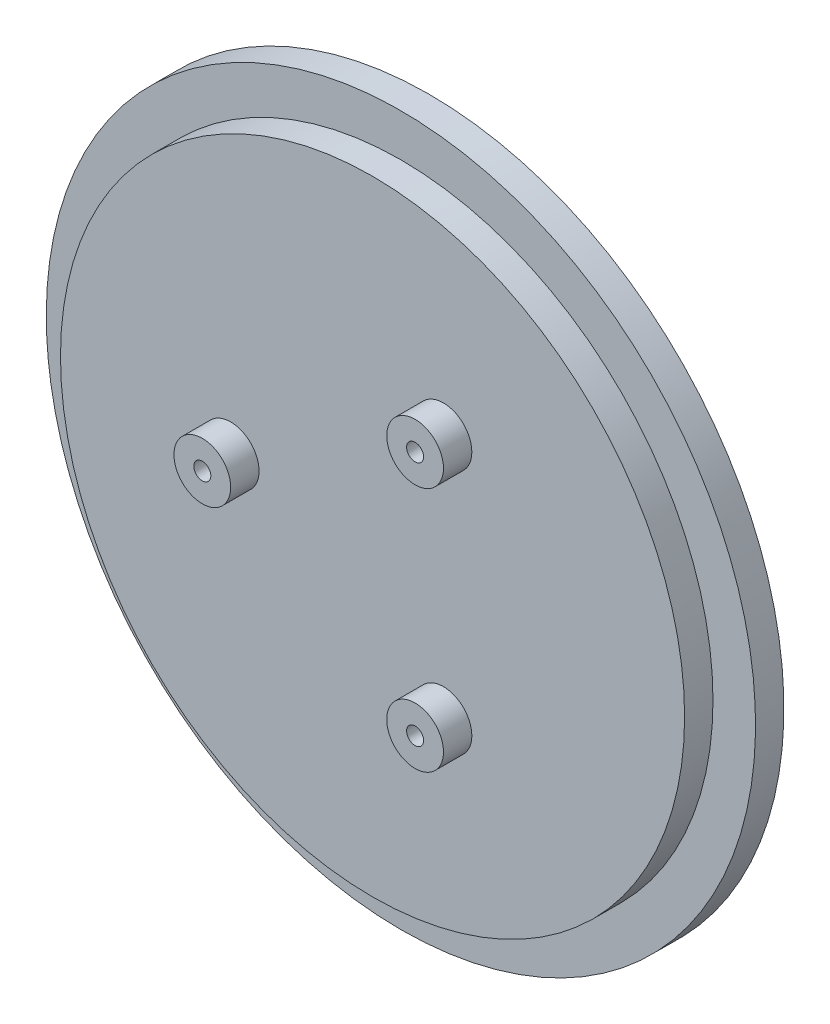
SolidWorks part; units mm, degrees
ref_plane "前视基准面" through (0, 0, 0) normal (0, 0, 1) x (1, 0, 0)
ref_plane "上视基准面" through (0, 0, 0) normal (0, 1, 0) x (1, 0, 0)
ref_plane "右视基准面" through (0, 0, 0) normal (1, 0, 0) x (0, 0, -1)
sketch "草图1" plane through (0, 0, 0) normal (0, 0, 1) x (1, 0, 0)
  circle A0 centre (0, 0) radius 22
extrude "凸台-拉伸1" add sketch "草图1" along normal blind 2
sketch "草图2" plane through (0, 0, 2) normal (0, 0, 1) x (1, 0, 0)
  circle A1 centre (-10, 0) radius 0.6
  circle A2 centre (5, -8.6603) radius 0.6
  circle A3 centre (5, 8.6603) radius 0.6
  circle A4 centre (-10, 0) radius 2
  circle A5 centre (5, 8.6603) radius 2
  circle A6 centre (5, -8.6603) radius 2
extrude "凸台-拉伸2" add sketch "草图2" along normal blind 4
sketch "草图3" plane through (0, 0, 0) normal (0, 0, -1) x (-1, 0, 0)
  circle A0 centre (0, 0) radius 25
extrude "凸台-拉伸3" add sketch "草图3" along normal blind 2
sketch "草图4" plane through (0, 0, -2) normal (0, 0, -1) x (-1, 0, 0)
  line L1 (-7.25, 3.95) -> (7.25, 3.95)
  line L3 (-7.25, -3.95) -> (7.25, -3.95)
  arc A2 (-7.25, 3.95) -> (-7.25, -3.95) centre (-7.25, 0) ccw
  arc A3 (7.25, 3.95) -> (7.25, -3.95) centre (7.25, 0) cw
  point P8 (0, 3.95)
  point P11 (0, -3.95)
extrude "切除-拉伸1" cut sketch "草图4" against normal blind 2
sketch "草图5" plane through (0, 0, -2) normal (0, 0, -1) x (-1, 0, 0)
  line L8 (28.3015, -3.95) -> (28.3015, 3.95)
  line L9 (21, 3.95) -> (28.3015, 3.95)
  line L10 (21, -3.95) -> (21, 3.95)
  line L11 (21, -3.95) -> (28.3015, -3.95)
extrude "切除-拉伸2" cut sketch "草图5" against normal blind 1
sketch "草图6" plane through (0, 0, -2) normal (0, 0, -1) x (-1, 0, 0)
  circle A2 centre (-18, 0) radius 5.45
  circle A3 centre (9, 15.5885) radius 5.45
  circle A4 centre (9, -15.5885) radius 5.45
  circle A5 centre (-18, 0) radius 3.85
  circle A6 centre (9, 15.5885) radius 3.85
  circle A7 centre (9, -15.5885) radius 3.85
  dimension "D1" = 3
extrude "切除-拉伸3" cut sketch "草图6" against normal blind 1.3
sketch "草图8" plane through (0, 0, 6) normal (0, 0, 1) x (1, 0, 0)
  circle A0 centre (5, -8.6603) radius 0.6
  circle A1 centre (-10, 0) radius 0.6
  circle A2 centre (5, 8.6603) radius 0.6
extrude "切除-拉伸4" cut sketch "草图8" against normal blind 18.5
sketch "草图9" plane through (0, 0, 6) normal (0, 0, 1) x (1, 0, 0)
  circle A0 centre (0, 0) radius 16.6958
extrude "切除-拉伸5" cut sketch "草图9" against normal blind 2
sketch "草图10" plane through (0, 0, -2) normal (0, 0, -1) x (-1, 0, 0)
  circle A0 centre (-5, -8.6603) radius 1.6
  circle A1 centre (-5, 8.6603) radius 1.6
extrude "切除-拉伸6" cut sketch "草图10" against normal blind 1
sketch "草图11" plane through (0, 0, -2) normal (0, 0, -1) x (-1, 0, 0)
  circle A0 centre (10, 0) radius 1.6
extrude "切除-拉伸7" cut sketch "草图11" against normal blind 3
